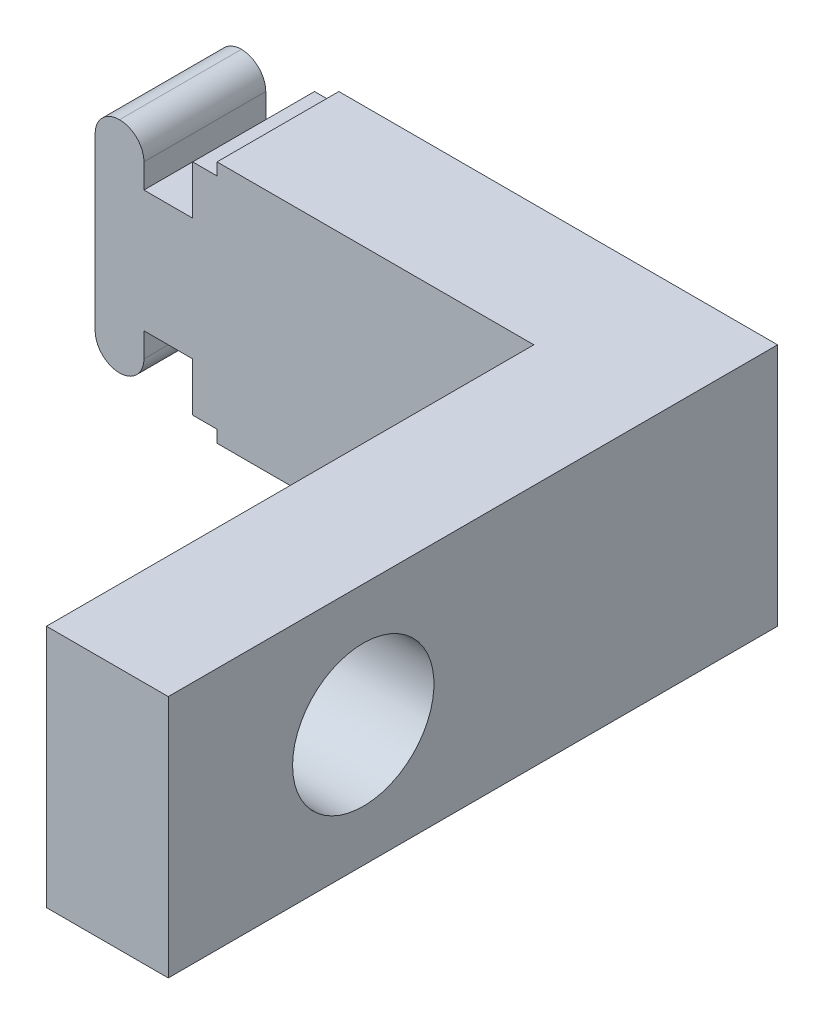
SolidWorks part; units mm, degrees
ref_plane "Front Plane" through (0, 0, 0) normal (0, 0, 1) x (1, 0, 0)
ref_plane "Top Plane" through (0, 0, 0) normal (0, 1, 0) x (1, 0, 0)
ref_plane "Right Plane" through (0, 0, 0) normal (1, 0, 0) x (0, 0, -1)
sketch "Sketch1" plane through (0, 0, 0) normal (0, 1, 0) x (1, 0, 0)
  line L0 (0, 0) -> (0, 31.75)
  line L1 (0, 31.75) -> (-22.86, 31.75)
  line L2 (-22.86, 31.75) -> (-22.86, 25.4)
  line L3 (-22.86, 25.4) -> (-6.35, 25.4)
  line L4 (-6.35, 25.4) -> (-6.35, 0)
  line L5 (-6.35, 0) -> (0, 0)
  dimension "D1" = 25.4
  dimension "D2" = 16.51
  dimension "D3" = 6.35
  dimension "D4" = 6.35
extrude "Boss-Extrude1" add sketch "Sketch1" along normal blind 12.7
sketch "Sketch2" plane through (-6.35, 0, 0) normal (-1, 0, 0) x (0, 0, 1)
  line L0 (0, 12.7) -> (0, 0) construction
  line L1 (-25.4, 12.7) -> (-25.4, 0) construction
  circle A0 centre (-10.16, 6.35) radius 3.683
  point P5 (0, 6.35)
  point P8 (-25.4, 6.35)
  dimension "D1" = 7.366
  dimension "D2" = 15.24
extrude "Cut-Extrude1" cut sketch "Sketch2" against normal blind 12.7
sketch "Sketch6" plane through (0, 0, -31.75) normal (0, 0, -1) x (-1, 0, 0)
  line L0 (22.86, 12.7) -> (22.86, 0) construction
  line L1 (16.51, 12.065) -> (29.21, 12.065)
  line L2 (16.51, 12.065) -> (16.51, 0.635)
  line L3 (16.51, 0.635) -> (29.21, 0.635)
  line L4 (29.21, 12.065) -> (29.21, 0.635)
  line L5 (16.51, 12.065) -> (29.21, 0.635) construction
  line L6 (16.51, 0.635) -> (29.21, 12.065) construction
  point P0 (22.86, 6.35)
  dimension "D1" = 11.43
  dimension "D2" = 12.7
extrude "Boss-Extrude2" add sketch "Sketch6" against normal up to surface (6.35 mm away) up to face at (-14.605, 6.35, -25.4)
sketch "Sketch9" plane through (0, 0, -31.75) normal (0, 0, -1) x (-1, 0, 0)
  line L0 (26.67, 12.065) -> (26.67, 9.525)
  line L1 (29.21, 12.065) -> (22.86, 12.065) construction
  line L2 (26.67, 9.525) -> (24.13, 9.525)
  line L3 (24.13, 9.525) -> (24.13, 12.065)
  line L4 (24.13, 12.065) -> (26.67, 12.065)
  line L5 (22.86, 0.635) -> (29.21, 0.635) construction
  line L6 (26.67, 0.635) -> (26.67, 3.175)
  line L7 (26.67, 3.175) -> (24.13, 3.175)
  line L8 (24.13, 3.175) -> (24.13, 0.635)
  line L9 (24.13, 0.635) -> (26.67, 0.635)
  dimension "D1" = 2.54
  dimension "D2" = 2.54
  dimension "D3" = 2.54
  dimension "D4" = 2.54
extrude "Cut-Extrude2" cut sketch "Sketch9" against normal up to surface (6.35 mm away) up to face at (-20.32, 6.35, -25.4)
fillet "Fillet1" radius 1.27 4 edges at (-26.67, 12.065, -28.575) (-29.21, 12.065, -28.575) (-26.67, 0.635, -28.575) (-29.21, 0.635, -28.575)
